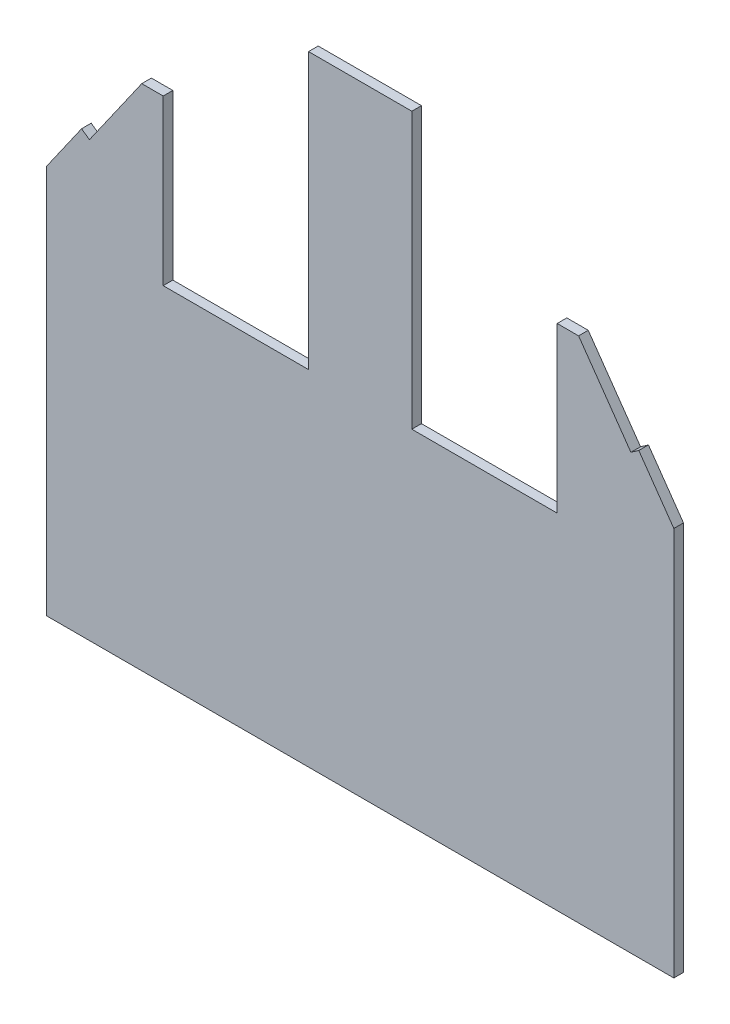
SolidWorks part; units mm, degrees
ref_plane "Front Plane" through (0, 0, 0) normal (0, 0, 1) x (1, 0, 0)
ref_plane "Top Plane" through (0, 0, 0) normal (0, 1, 0) x (1, 0, 0)
ref_plane "Right Plane" through (0, 0, 0) normal (1, 0, 0) x (0, 0, -1)
sketch "Sketch1" plane through (0, 0, 0) normal (0, 0, 1) x (1, 0, 0)
  line L0 (25.1529, 44.8276) -> (28.7099, 44.8276)
  line L1 (41.554, 35.341) -> (37.3927, 32.4273)
  line L2 (37.3057, 35.341) -> (44.5204, 25.0374)
  line L3 (25.1529, 49.9076) -> (37.3927, 32.4273)
  line L12 (-40.2521, 49.9076) -> (-40.2521, 17.561)
  line L13 (-40.2521, 17.561) -> (-16.1221, 17.561)
  line L14 (-16.1221, 17.561) -> (-16.1221, 63.281)
  line L15 (-16.1221, 60.741) -> (-32.6664, 60.741)
  line L16 (17.7677, 69.3114) -> (17.7677, 60.741)
  line L17 (-32.867, 69.3114) -> (-32.867, 60.741)
  line L18 (17.7677, 63.281) -> (-32.867, 63.281)
  line L24 (1.0229, 63.281) -> (1.0229, 17.561)
  line L25 (1.0229, 17.561) -> (25.1529, 17.561)
  line L26 (25.1529, 17.561) -> (25.1529, 49.9076)
  line L27 (17.5672, 60.741) -> (1.0229, 60.741)
  line L33 (-32.6664, 60.741) -> (-40.2521, 49.9076)
  line L37 (-32.867, 69.3114) -> (-62.716, 26.6826)
  line L43 (25.1529, 49.9076) -> (17.5672, 60.741)
  line L85 (46.3713, 28.4611) -> (19.5707, 66.7364)
  line L86 (46.3713, 28.4611) -> (19.5707, 66.7364)
  line L87 (-34.67, 66.7364) -> (-61.4706, 28.4611)
  line L95 (44.5204, -40.859) -> (44.5204, 31.1046)
  line L96 (-59.6196, -40.859) -> (-59.6196, 31.1046)
  line L97 (47.0604, -39.589) -> (-62.1596, -39.589)
  line L98 (-40.2521, 49.9076) -> (-52.4919, 32.4273)
  line L99 (-40.2521, 44.8276) -> (-43.8092, 44.8276)
  line L100 (-56.6532, 35.341) -> (-52.4919, 32.4273)
  line L101 (-52.4049, 35.341) -> (-59.6196, 25.0374)
  line L145 (47.0604, -40.859) -> (47.0604, 26.2758)
  line L146 (16.4498, 68.361) -> (-31.549, 68.361)
  line L147 (16.4498, 68.361) -> (-31.549, 68.361)
  line L150 (-62.1596, -40.859) -> (47.0604, -40.859)
  line L154 (-62.1596, -40.859) -> (47.0604, -40.859)
  line L155 (-62.1596, 26.2758) -> (-62.1596, -40.859)
  line L159 (47.0604, -40.859) -> (47.0604, 26.2758)
  line L169 (-62.1596, 26.2758) -> (-62.1596, -40.859)
  line L298 (25.1529, 35.341) -> (43.7195, 35.341)
  line L299 (-7.5496, 55.661) -> (-7.5496, -2.759) construction
  line L300 (-40.2521, 35.341) -> (-58.8188, 35.341)
  arc A14 (-61.4706, 28.4611) -> (-62.1596, 26.2758) centre (-58.3496, 26.2758) ccw
  arc A15 (-61.4706, 28.4611) -> (-62.1596, 26.2758) centre (-58.3496, 26.2758) ccw
  arc A16 (47.0604, 26.2758) -> (46.3713, 28.4611) centre (43.2504, 26.2758) ccw
  arc A17 (47.0604, 26.2758) -> (46.3713, 28.4611) centre (43.2504, 26.2758) ccw
  arc A18 (19.5707, 66.7364) -> (16.4498, 68.361) centre (16.4498, 64.551) ccw
  arc A19 (19.5707, 66.7364) -> (16.4498, 68.361) centre (16.4498, 64.551) ccw
  arc A20 (-31.549, 68.361) -> (-34.67, 66.7364) centre (-31.549, 64.551) ccw
  arc A21 (-31.549, 68.361) -> (-34.67, 66.7364) centre (-31.549, 64.551) ccw
  dimension "D5" = 5.08
  dimension "D6" = 2.54
  dimension "D9" = 5.08
  dimension "D10" = 1.6
  dimension "D1" = 2.54
extrude "Boss-Extrude1" add sketch "Sketch1" along normal blind 1.6 contours L300 L169 L154 L159 L298 L26 L25 L24 L27 L16 L17 L15 L14 L13 L12 | L26 L298 L3 L0 | L300 L12 L99 L98 region at (28.8593, 39.3209, 0) region at (-7.5496, -2.4996, 0) region at (-43.9586, 39.3209, 0)
sketch "Sketch2" plane through (0, 0, 0) normal (0, 0, -1) x (-1, 0, 0)
  line L1 (62.1596, -40.859) -> (-47.0604, -40.859)
  line L2 (62.1596, -40.859) -> (62.1596, 63.281)
  line L3 (62.1596, 63.281) -> (-47.0604, 63.281)
  line L4 (-47.0604, -40.859) -> (-47.0604, 63.281)
  arc A0 (-49.6004, -40.859) -> (-47.0604, -43.399) centre (-47.0604, -40.859) ccw construction
